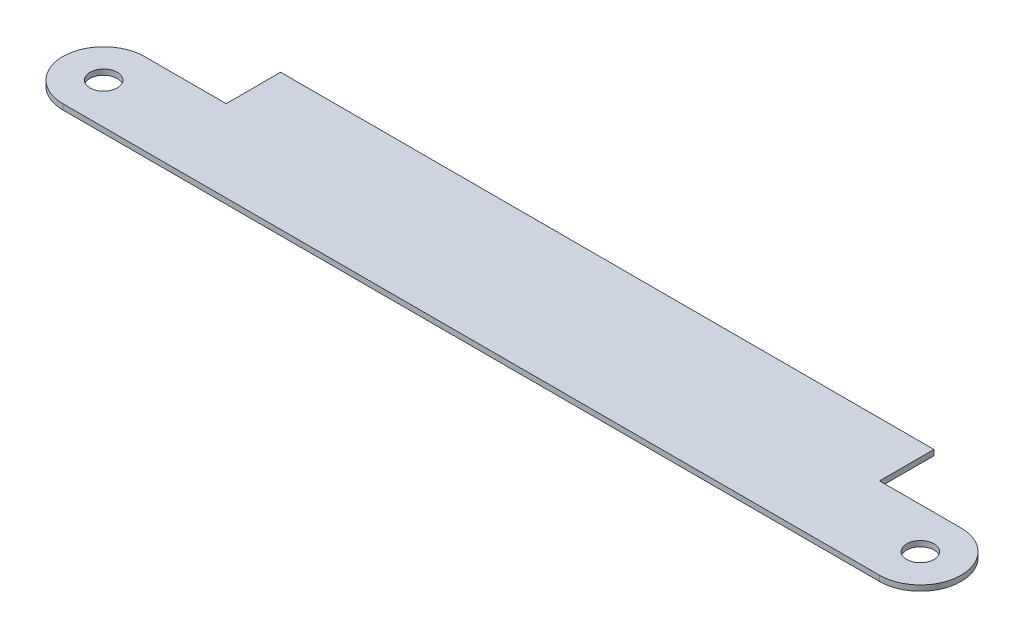
SolidWorks part; units mm, degrees
ref_plane "Front Plane" through (0, 0, 0) normal (0, 0, 1) x (1, 0, 0)
ref_plane "Top Plane" through (0, 0, 0) normal (0, 1, 0) x (1, 0, 0)
ref_plane "Right Plane" through (0, 0, 0) normal (1, 0, 0) x (0, 0, -1)
sketch "Sketch1" plane through (0, 0, 0) normal (0, 1, 0) x (1, 0, 0)
  line L0 (0, 0) -> (150, 0) construction
  line L1 (0, 7.5) -> (15, 7.5)
  line L2 (0, 7.5) -> (150, 7.5) construction
  line L3 (0, 7.5) -> (0, -7.5) construction
  line L4 (0, -7.5) -> (150, -7.5)
  line L5 (150, 7.5) -> (150, -7.5) construction
  line L6 (0, 7.5) -> (150, -7.5) construction
  line L7 (0, -7.5) -> (150, 7.5) construction
  line L8 (15, 7.5) -> (15, 17.5)
  line L9 (15, 17.5) -> (135, 17.5)
  line L10 (135, 17.5) -> (135, 7.5)
  line L11 (135, 7.5) -> (150, 7.5)
  line L12 (75, 0) -> (75, 17.5) construction
  circle A0 centre (0, 0) radius 2.5
  circle A1 centre (150, 0) radius 2.5
  arc A2 (0, 7.5) -> (0, -7.5) centre (0, 0) ccw
  arc A3 (150, -7.5) -> (150, 7.5) centre (150, 0) ccw
  point P5 (75, 0)
  dimension "D3" = 5
  dimension "D1" = 150
  dimension "D2" = 15
  dimension "D4" = 10
  dimension "D5" = 15
extrude "Boss-Extrude1" add sketch "Sketch1" along normal blind 1
